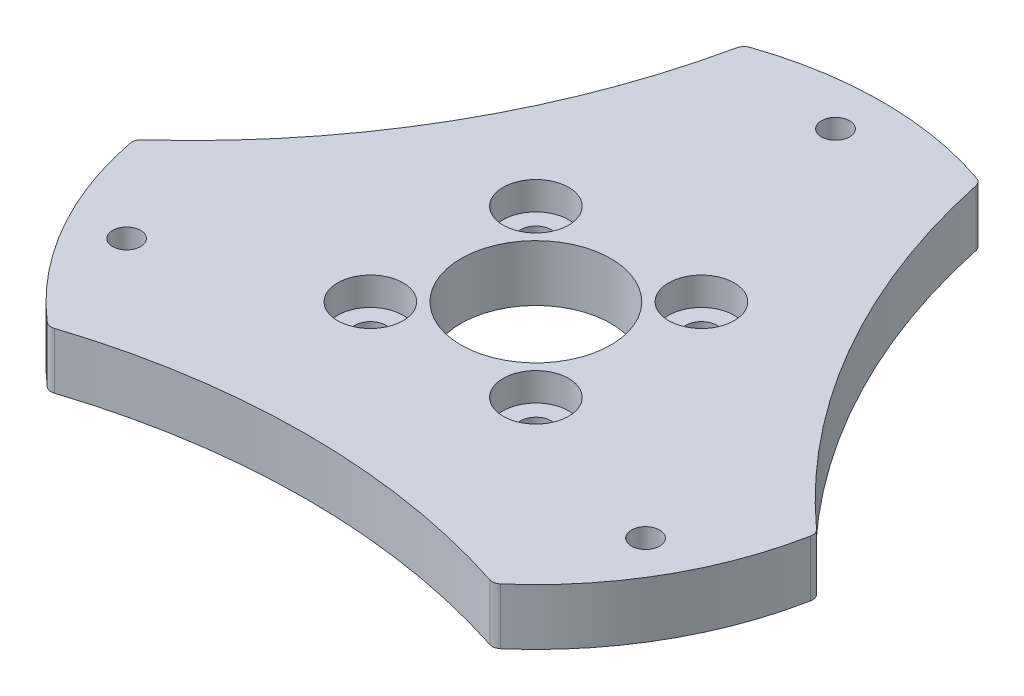
SolidWorks part; units mm, degrees
ref_plane "Front Plane" through (0, 0, 0) normal (0, 0, 1) x (1, 0, 0)
ref_plane "Top Plane" through (0, 0, 0) normal (0, 1, 0) x (1, 0, 0)
ref_plane "Right Plane" through (0, 0, 0) normal (1, 0, 0) x (0, 0, -1)
sketch "Sketch1" plane through (0, 0, 0) normal (0, 1, 0) x (1, 0, 0)
  circle A0 centre (0, 0) radius 37
  dimension "D1" = 74
extrude "Boss-Extrude1" add sketch "Sketch1" along normal blind 6
sketch "Sketch2" plane through (0, 0, 0) normal (0, 1, 0) x (1, 0, 0)
  line L0 (-12.6547, 34.7686) -> (0, 0) construction
  line L1 (0, 0) -> (12.6547, 34.7686) construction
  line L2 (0, -1000) -> (0, 49000) construction
  line L3 (-12.6547, 34.7686) -> (-9.9186, 27.2511)
  line L4 (12.6547, 34.7686) -> (9.9186, 27.2511)
  line L5 (36.4379, -6.425) -> (28.5594, -5.0358)
  line L6 (23.7831, -28.3436) -> (18.6408, -22.2153)
  line L7 (-23.7831, -28.3436) -> (-18.6408, -22.2153)
  line L8 (-36.4379, -6.425) -> (-28.5594, -5.0358)
  circle A0 centre (0, 0) radius 37 construction
  arc A1 (-12.6547, 34.7686) -> (12.6547, 34.7686) centre (0, 0) cw
  arc A2 (-9.9186, 27.2511) -> (9.9186, 27.2511) centre (0, 0) cw
  arc A3 (36.4379, -6.425) -> (23.7831, -28.3436) centre (0, 0) cw
  arc A4 (28.5594, -5.0358) -> (18.6408, -22.2153) centre (0, 0) cw
  arc A5 (-23.7831, -28.3436) -> (-36.4379, -6.425) centre (0, 0) cw
  arc A6 (-18.6408, -22.2153) -> (-28.5594, -5.0358) centre (0, 0) cw
  point P21 (0, 0)
  dimension "D1" = 20
  dimension "D2" = 20
  dimension "D3" = 8
  dimension "D4" = 3
sketch "Sketch3" plane through (0, 6, 0) normal (0, 1, 0) x (1, 0, 0)
  circle A0 centre (86.6025, 50) radius 75.5001
  dimension "D1" = 100
extrude "Cut-Extrude1" cut sketch "Sketch3" against normal through all
sketch "Sketch5" plane through (0, 6, 0) normal (0, 1, 0) x (1, 0, 0)
  line L0 (0, -1000) -> (0, 49000) construction
  line L1 (0, 32) -> (0, 0) construction
  circle A0 centre (0, 32) radius 1.5
  dimension "D2" = 3
  dimension "D1" = 32
  dimension "D3" = 0
extrude "Cut-Extrude2" cut sketch "Sketch5" against normal through all
pattern_circular "CirPattern1" count 3 over 360 about axis through (0, 6, 0) along (0, -1, 0) of "Cut-Extrude1", "Cut-Extrude2" reverse direction yes
sketch "Sketch6" plane through (0, 6, 0) normal (0, 1, 0) x (1, 0, 0)
  line L1 (-8.8388, -8.8388) -> (8.8388, -8.8388) construction
  line L2 (-8.8388, -8.8388) -> (-8.8388, 8.8388) construction
  line L3 (-8.8388, 8.8388) -> (8.8388, 8.8388) construction
  line L4 (8.8388, -8.8388) -> (8.8388, 8.8388) construction
  line L5 (-8.8388, -8.8388) -> (8.8388, 8.8388) construction
  line L6 (-8.8388, 8.8388) -> (8.8388, -8.8388) construction
  circle A0 centre (8.8388, 8.8388) radius 1.65
  circle A1 centre (-8.8388, 8.8388) radius 1.65
  circle A2 centre (-8.8388, -8.8388) radius 1.65
  circle A3 centre (8.8388, -8.8388) radius 1.65
  point P0 (0, 0)
  dimension "D1" = 3.3
  dimension "D2" = 12.5
extrude "Cut-Extrude3" cut sketch "Sketch6" against normal through all
sketch "Sketch7" plane through (0, 6, 0) normal (0, 1, 0) x (1, 0, 0)
  circle A0 centre (0, 0) radius 8
  dimension "D1" = 16
extrude "Cut-Extrude4" cut sketch "Sketch7" against normal through all
fillet "Fillet1" radius 1 6 edges at (-36.4379, 3, 6.425) (-12.6547, 3, -34.7686) (23.7831, 3, 28.3436) (-23.7831, 3, 28.3436) (36.4379, 3, 6.425) (12.6547, 3, -34.7686)
sketch "Sketch8" plane through (0, 6, 0) normal (0, -1, 0) x (1, 0, 0)
  circle A0 centre (8.8388, 8.8388) radius 3.5
  circle A1 centre (8.8388, -8.8388) radius 3.5
  circle A2 centre (-8.8388, 8.8388) radius 3.5
  circle A3 centre (-8.8388, -8.8388) radius 3.5
  dimension "D1" = 7
extrude "Cut-Extrude5" cut sketch "Sketch8" along normal blind 3
